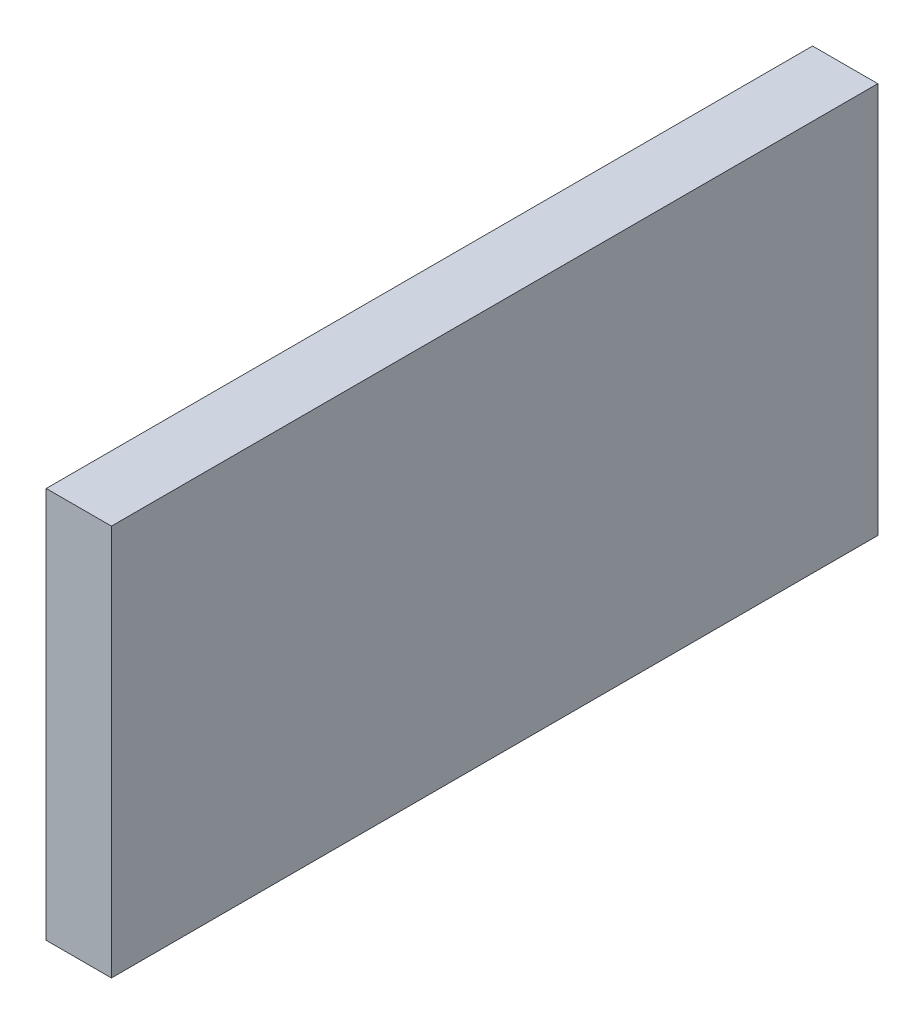
SolidWorks part; units mm, degrees
material "Acrylic (Medium-high impact)"
ref_plane "Front Plane" through (0, 0, 0) normal (0, 0, 1) x (1, 0, 0)
ref_plane "Top Plane" through (0, 0, 0) normal (0, 1, 0) x (1, 0, 0)
ref_plane "Right Plane" through (0, 0, 0) normal (1, 0, 0) x (0, 0, -1)
sketch "Sketch1" plane through (0, 0, 39.2805) normal (0, 0, 1) x (1, 0, 0)
  line L0 (13.9215, 29.1718) -> (8.9215, 29.1718) construction
  line L1 (8.9215, 47.1718) -> (11.9215, 47.1718)
  line L2 (8.9215, 47.1718) -> (8.9215, 29.1718)
  line L3 (8.9215, 29.1718) -> (11.9215, 29.1718)
  line L4 (11.9215, 47.1718) -> (11.9215, 29.1718)
  dimension "D1" = 3
extrude "Boss-Extrude1" add sketch "Sketch1" along normal up to surface (35.25 mm away)
